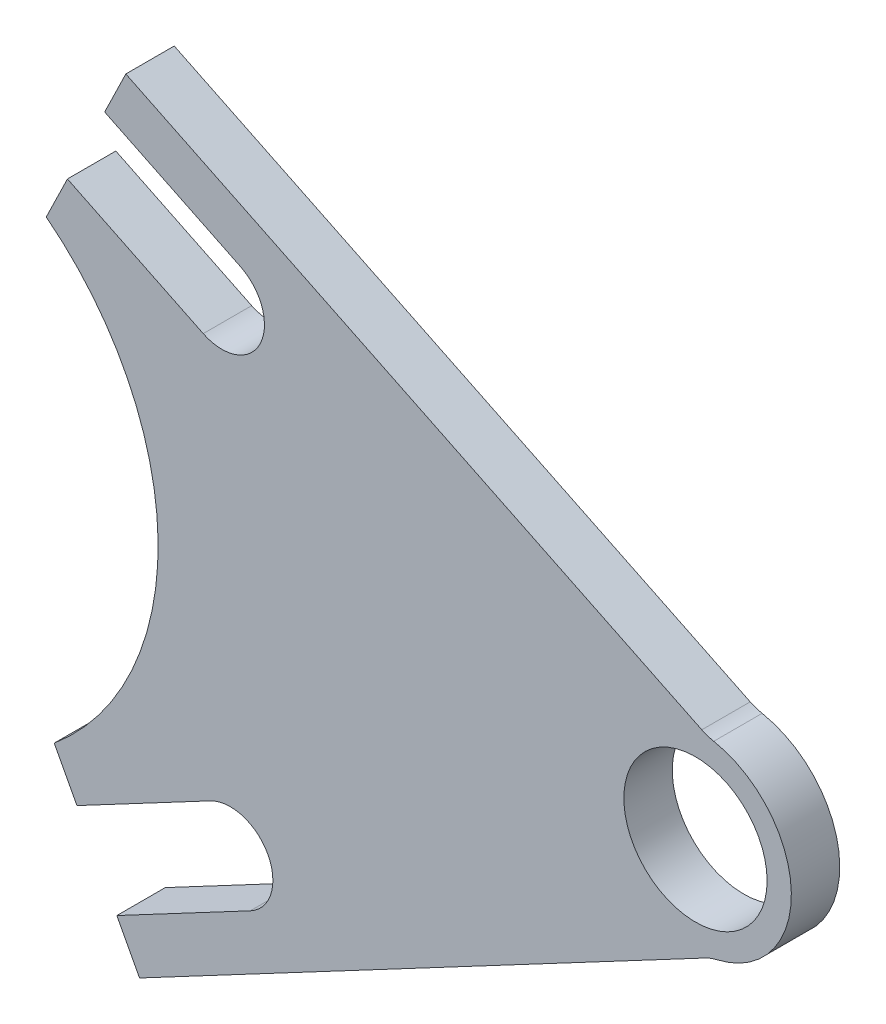
SolidWorks part; units mm, degrees
ref_plane "Front" through (0, 0, 0) normal (0, 0, 1) x (1, 0, 0)
ref_plane "Top" through (0, 0, 0) normal (0, 1, 0) x (1, 0, 0)
ref_plane "Right" through (0, 0, 0) normal (1, 0, 0) x (0, 0, -1)
sketch "Sketch1" plane through (0, 0, 0) normal (0, 0, 1) x (1, 0, 0)
  line L0 (628.4169, 6.6657) -> (571.3072, 34.4277) construction
  line L1 (328.6246, 152.4) -> (628.4169, 6.6657) construction
  line L2 (628.4169, 6.6657) -> (572.3237, -23.0966) construction
  line L3 (328.6246, -152.4) -> (628.4169, 6.6657) construction
  line L4 (568.7246, 41.8964) -> (566.2815, 36.8708) construction
  line L5 (566.2815, 36.8708) -> (563.8385, 31.8451) construction
  line L6 (568.7246, 41.8964) -> (550.9064, 50.5582)
  line L7 (563.8385, 31.8451) -> (546.0203, 40.5069)
  line L8 (546.0203, 40.5069) -> (543.2441, 34.7959)
  line L9 (550.9064, 50.5582) -> (553.6826, 56.2692)
  line L10 (553.6826, 56.2692) -> (630.0737, 19.1341)
  line L11 (543.2441, 34.7959) -> (619.6352, -2.3392)
  line L12 (564.7684, -20.7795) -> (547.2673, -30.0654)
  line L13 (547.2673, -30.0654) -> (544.291, -24.456)
  line L14 (544.291, -24.456) -> (619.3225, 15.3547)
  line L15 (570.0065, -30.6519) -> (552.5054, -39.9378)
  line L16 (552.5054, -39.9378) -> (555.4817, -45.5471)
  line L17 (555.4817, -45.5471) -> (630.5132, -5.7364)
  arc A0 (568.7246, 41.8964) -> (563.8385, 31.8451) centre (566.2815, 36.8708) cw
  arc A1 (564.7684, -20.7795) -> (570.0065, -30.6519) centre (567.3874, -25.7157) cw
  circle A2 centre (628.4169, 6.6657) radius 9.398
  circle A3 centre (628.4169, 6.6657) radius 12.578
  point P14 (572.3237, -23.0966)
  point P16 (571.3072, 34.4277)
  dimension "D1" = 18.796
  dimension "D2" = 3.18
  dimension "D3" = 11.938
  dimension "D4" = 6.35
  dimension "D5" = 63.5
  dimension "D6" = 25.4
extrude "Boss-Extrude1" add sketch "Sketch1" along normal mid plane 6.35 contours A3 L10 L9 L6 A0 L7 L8 L11 L14 | A3 L14 L11 | A3 A2 | A3 L11 L14 L13 L12 A1 L15 L16 L17 region at (586.2187, 27.7878, 0) region at (637.6109, 14.7188, 0) region at (611.9263, 6.3743, 0) region at (586.9912, -15.9341, 0)
fillet "Fillet1" radius 38.1 1 edges at (602.0689, 6.2001, 0)
fillet "Fillet2" radius 6.35 2 edges at (630.5132, -5.7364, 0) (630.0737, 19.1341, 0)
